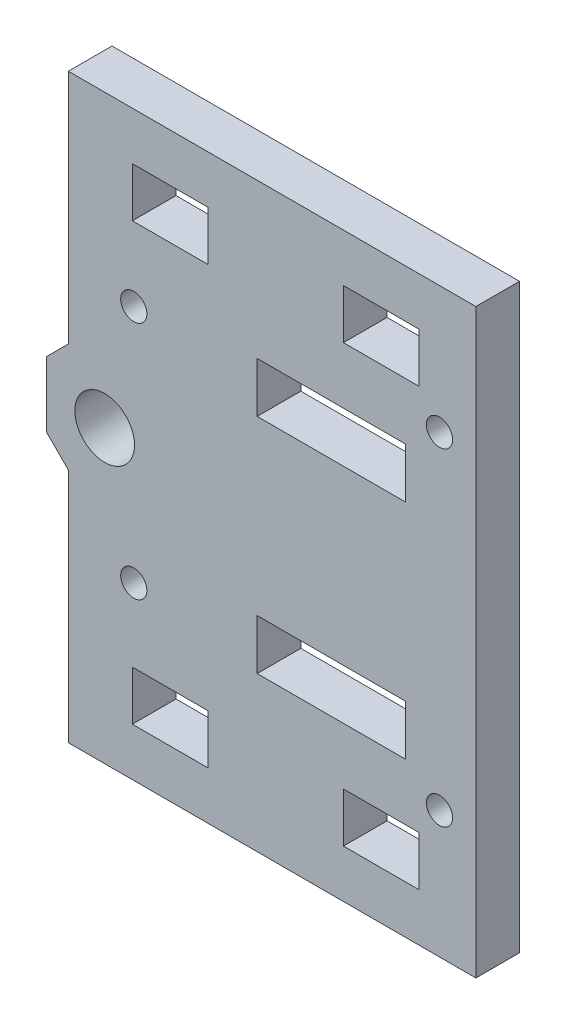
SolidWorks part; units mm, degrees
ref_plane "Plano frontal" through (0, 0, 0) normal (0, 0, 1) x (1, 0, 0)
ref_plane "Plano superior" through (0, 0, 0) normal (0, 1, 0) x (1, 0, 0)
ref_plane "Plano direito" through (0, 0, 0) normal (1, 0, 0) x (0, 0, -1)
sketch "Model" plane through (0, 0, 0) normal (0, 0, 1) x (1, 0, 0)
  line L0 (86.2842, 87.3657) -> (30.2842, 87.3657)
  line L1 (56.2332, 28.6657) -> (56.2332, 35.5657)
  line L2 (76.6016, 35.5657) -> (76.6016, 28.6657)
  line L3 (49.4842, 14.0657) -> (49.4842, 20.8657)
  line L4 (39.0842, 20.8657) -> (49.4842, 20.8657)
  line L5 (39.0842, 14.0657) -> (39.0842, 20.8657)
  line L6 (49.4842, 14.0657) -> (39.0842, 14.0657)
  line L7 (49.4842, 73.9657) -> (49.4842, 80.7657)
  line L8 (39.0842, 80.7657) -> (49.4842, 80.7657)
  line L9 (39.0842, 73.9657) -> (39.0842, 80.7657)
  line L10 (49.4842, 73.9657) -> (39.0842, 73.9657)
  line L11 (56.2332, 66.1657) -> (76.6016, 66.1657)
  line L12 (56.2332, 59.2657) -> (76.6016, 59.2657)
  line L13 (56.2332, 35.5657) -> (76.6016, 35.5657)
  line L14 (56.2332, 28.6657) -> (76.6016, 28.6657)
  line L15 (27.2842, 42.9266) -> (30.2842, 39.9266)
  line L16 (27.2842, 51.9048) -> (27.2842, 42.9266)
  line L17 (27.2842, 51.9048) -> (30.2842, 54.9048)
  line L18 (30.2842, 54.9048) -> (30.2842, 87.3657)
  line L19 (76.6016, 66.1657) -> (76.6016, 59.2657)
  line L20 (56.2332, 59.2657) -> (56.2332, 66.1657)
  line L21 (86.2842, 87.3657) -> (86.2842, 7.4657)
  line L22 (30.2842, 7.4657) -> (30.2842, 39.9266)
  line L23 (86.2842, 7.4657) -> (30.2842, 7.4657)
  line L24 (68.0842, 20.8657) -> (78.4842, 20.8657)
  line L25 (78.4842, 20.8657) -> (78.4842, 14.0657)
  line L26 (78.4842, 14.0657) -> (68.0842, 14.0657)
  line L27 (68.0842, 14.0657) -> (68.0842, 20.8657)
  line L28 (68.0842, 80.7657) -> (78.4842, 80.7657)
  line L29 (78.4842, 80.7657) -> (78.4842, 73.9657)
  line L30 (78.4842, 73.9657) -> (68.0842, 73.9657)
  line L31 (68.0842, 73.9657) -> (68.0842, 80.7657)
  circle A0 centre (39.2842, 30.9657) radius 1.8
  circle A1 centre (81.2842, 24.9157) radius 1.8
  circle A2 centre (81.2842, 69.9157) radius 1.8
  circle A3 centre (39.2842, 63.8657) radius 1.8
  circle A4 centre (35.2842, 47.4157) radius 4.1
extrude "Ressalto-extrusão1" add sketch "Model" along normal blind 6
